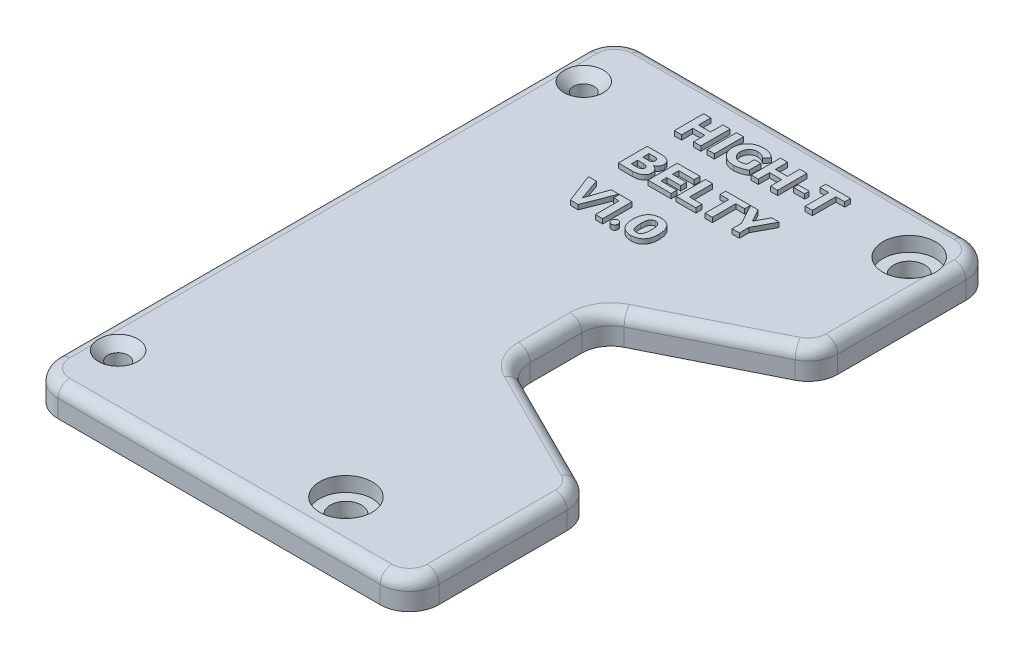
SolidWorks part; units mm, degrees
ref_plane "Front Plane" through (0, 0, 0) normal (0, 0, 1) x (1, 0, 0)
ref_plane "Top Plane" through (0, 0, 0) normal (0, 1, 0) x (1, 0, 0)
ref_plane "Right Plane" through (0, 0, 0) normal (1, 0, 0) x (0, 0, -1)
sketch "Sketch2" plane through (0, 0, 0) normal (0, 1, 0) x (1, 0, 0)
  line L1 (-32.5, 50) -> (32.5, 50)
  line L2 (-32.5, 50) -> (-32.5, -50)
  line L3 (-32.5, -50) -> (32.5, -50)
  line L4 (32.5, 50) -> (32.5, -50)
  line L5 (-32.5, 50) -> (32.5, -50) construction
  line L6 (-32.5, -50) -> (32.5, 50) construction
  circle A0 centre (-27.5, 39.75) radius 1.75
  circle A1 centre (-27.5, -39.75) radius 1.75
  circle A2 centre (26.23, 41.58) radius 2.65
  circle A3 centre (13.65, -42) radius 2.65
  point P0 (0, 0)
  dimension "D3" = 3.5
  dimension "D4" = 5
  dimension "D8" = 5.3
  dimension "D9" = 5.3
  dimension "D1" = 65
  dimension "D2" = 100
  dimension "D5" = 5
  dimension "D6" = 10.25
  dimension "D7" = 10.25
  dimension "D10" = 46.15
  dimension "D11" = 8
  dimension "D12" = 8.42
  dimension "D13" = 6.27
extrude "Boss-Extrude1" add sketch "Sketch2" along normal blind 5
sketch "Sketch3" plane through (0, 5, 0) normal (0, 1, 0) x (1, 0, 0)
  circle A0 centre (26.23, 41.58) radius 4.5
  circle A1 centre (13.65, -42) radius 4.5
  dimension "D1" = 9
  dimension "D2" = 9
extrude "Cut-Extrude1" cut sketch "Sketch3" against normal blind 2.5
fillet "Fillet1" radius 5 4 edges at (-32.5, 2.5, 50) (-32.5, 2.5, -50) (32.5, 2.5, -50) (32.5, 2.5, 50)
chamfer "Chamfer1" distance 1.6 angle 45 2 edges at (-27.5, 5, 41.5) (-27.5, 5, -38)
sketch "Sketch6" plane through (0, 5, 0) normal (0, 1, 0) x (1, 0, 0)
  line L0 (7.5, 7.5) -> (32.5, 20)
  line L1 (32.5, -45) -> (32.5, 45) construction
  line L2 (32.5, 20) -> (32.5, -20)
  line L3 (32.5, -20) -> (7.5, -7.5)
  line L4 (7.5, -7.5) -> (7.5, 7.5)
  point P4 (7.5, 0)
  dimension "D1" = 25
  dimension "D2" = 40
  dimension "D3" = 15
extrude "Cut-Extrude2" cut sketch "Sketch6" against normal through all
fillet "Fillet3" radius 5 4 edges at (32.5, 2.5, -20) (7.5, 2.5, -7.5) (7.5, 2.5, 7.5) (32.5, 2.5, 20)
fillet "Fillet2" radius 2 16 edges at (-31.0355, 5, 48.5355) (-32.5, 5, 0) (-31.0355, 5, -48.5355) (0, 5, -50) (31.0355, 5, -48.5355) (32.5, 5, -34.0451) (32.5, 5, 34.0451) (31.0355, 5, 48.5355) (0, 5, 50) (31.7533, 5, -20.4615) (20, 5, -13.75) (8.2467, 5, -7.0385) (7.5, 5, 0) (8.2467, 5, 7.0385) (20, 5, 13.75) (31.7533, 5, 20.4615)
sketch "Sketch4" plane through (0, 5, 0) normal (0, 1, 0) x (1, 0, 0)
  text T0 "<b>HIGH-T</b>\r\n<b>BELTY</b>\r\n<b>V1.0</b>" font "Montserrat" height 5
  point P1 (-12.9369, 34.7464)
  point P2 (-12.5123, 35.9419)
  point P3 (-11.646, 39.1101)
  point P4 (-12.2303, 39.4022)
extrude "Boss-Extrude2" add sketch "Sketch4" along normal blind 0.8
